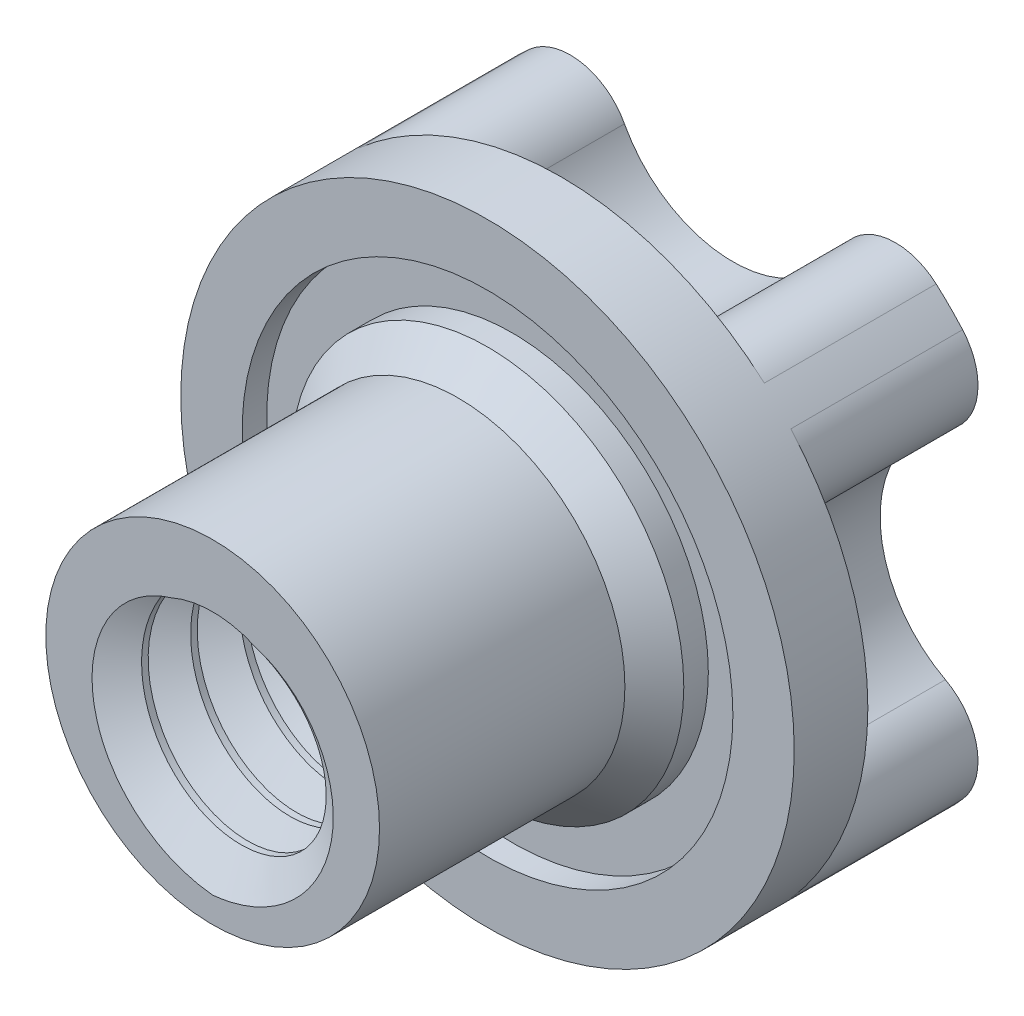
SolidWorks part; units mm, degrees
ref_plane "Спереди" through (0, 0, 0) normal (0, 0, 1) x (1, 0, 0)
ref_plane "Сверху" through (0, 0, 0) normal (0, 1, 0) x (1, 0, 0)
ref_plane "Справа" through (0, 0, 0) normal (1, 0, 0) x (0, 0, -1)
sketch "Эскиз1" plane through (0, 0, 0) normal (0, 1, 0) x (1, 0, 0)
  line L0 (0, 0) -> (0, 30.0583) construction
  line L1 (0, 0) -> (-4.25, 0) construction
  line L2 (-4.25, 0) -> (-6.8, 0)
  line L3 (-6.8, 0) -> (-6.8, 10)
  line L4 (-6.8, 10) -> (-8, 11.2)
  line L5 (-8, 11.2) -> (-8, 12.2)
  line L6 (-12.5, 21.2) -> (-4.25, 21.2)
  line L7 (-4.25, 21.2) -> (-4.25, 0)
  line L8 (-8, 12.2) -> (-10, 12.2)
  line L9 (-10, 12.2) -> (-10, 11.2)
  line L10 (-10, 11.2) -> (-12.5, 11.2)
  line L11 (-12.5, 11.2) -> (-12.5, 21.2)
  line L12 (-8, 11.2) -> (-10, 11.2) construction
  dimension "D1" = 8.5
  dimension "D2" = 13.6
  dimension "D3" = 10
  dimension "D4" = 16
  dimension "D5" = 45
  dimension "D6" = 1
  dimension "D7" = 20
  dimension "D8" = 25
  dimension "D9" = 10
revolve "Повернуть1" add sketch "Эскиз1" angle 360 about L0
sketch "Эскиз2" plane through (0, 0, 0) normal (0, 0, 1) x (1, 0, 0)
  circle A0 centre (0, 0) radius 5
  dimension "D1" = 10
curve "Спираль1" pitch 2 height 30 radius 5 centre (0, 0, 0) axis (0, 0, -1) start towards (0, 1, 0)
sketch "Эскиз3" plane through (0, 0, 0) normal (1, 0, 0) x (0, 0, -1)
  line L0 (-5, 5.75) -> (-5.95, 4.1046)
  line L1 (-5, 5.75) -> (-4.05, 4.1046)
  line L2 (-4.05, 4.1046) -> (-5.95, 4.1046)
  line L3 (0, 0) -> (-6.7976, 0) construction
  line L4 (-5, 5.75) -> (-5, 4.1046) construction
  dimension "D1" = 11.5
  dimension "D2" = 60
  dimension "D3" = 1.9
  dimension "D4" = 5
sweep "Вырез-По траектории13" cut profiles "Эскиз3" path "Спираль1"
sketch "Эскиз4" plane through (0, 0, -21.2) normal (0, 0, -1) x (-1, 0, 0)
  circle A0 centre (0, -11) radius 5
  circle A1 centre (0, 0) radius 11 construction
  circle A2 centre (-11, 0) radius 5
  circle A3 centre (0, 11) radius 5
  circle A4 centre (11, 0) radius 5
  point P14 (0, 0)
  dimension "D1" = 22
  dimension "D2" = 10
  dimension "D3" = 4
extrude "Вырез-Вытянуть1" cut sketch "Эскиз4" against normal blind 7
fillet "Скругление1" radius 2.5 8 edges at (-4.9782, -11.4659, -17.7) (-11.4659, -4.9782, -17.7) (4.9782, -11.4659, -17.7) (11.4659, -4.9782, -17.7) (11.4659, 4.9782, -17.7) (4.9782, 11.4659, -17.7) (-4.9782, 11.4659, -17.7) (-11.4659, 4.9782, -17.7)
sketch "Эскиз5" plane through (0, 0, 0) normal (1, 0, 0) x (0, 0, -1)
  line L1 (14.6674, 22.9937) -> (-9.6567, 22.9937)
  line L2 (14.6674, 22.9937) -> (14.6674, -22.4524)
  line L3 (14.6674, -22.4524) -> (-9.6567, -22.4524)
  line L4 (-9.6567, 22.9937) -> (-9.6567, -22.4524)
extrude "Вырез-Вытянуть2" [suppressed] cut sketch "Эскиз5" against normal through all and the other way through all
